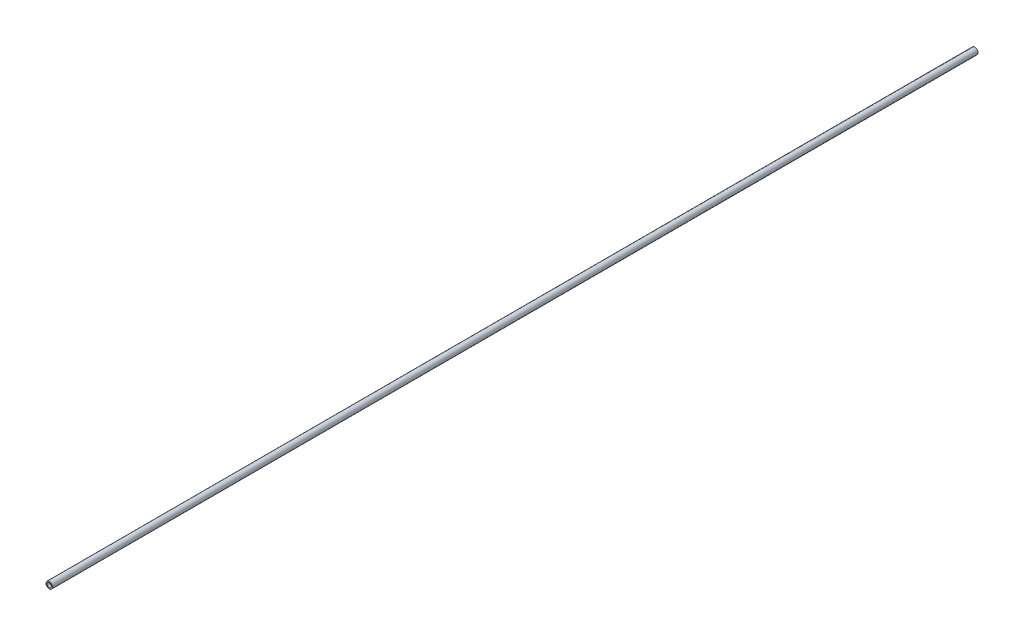
SolidWorks part; units mm, degrees
material "PVC Rigid"
ref_plane "Front" through (0, 0, 0) normal (0, 0, 1) x (1, 0, 0)
ref_plane "Top" through (0, 0, 0) normal (0, 1, 0) x (1, 0, 0)
ref_plane "Side" through (0, 0, 0) normal (1, 0, 0) x (0, 0, -1)
sketch "PipeSketch" plane through (0, 0, 0) normal (0, 0, 1) x (1, 0, 0)
  circle A0 centre (0, 0) radius 10.668
  circle A1 centre (0, 0) radius 6.9342
  dimension "OuterDiameter" = 21.336
  dimension "InnerDiameter" = 13.8684
extrude "Extrusion" add sketch "PipeSketch" along normal blind 3048
sketch "FilterSketch" plane through (0, 0, 0) normal (0, 0, 1) x (1, 0, 0)
  circle A0 centre (0, 0) radius 6.35 construction
  dimension "NominalDiameter" = 12.7
